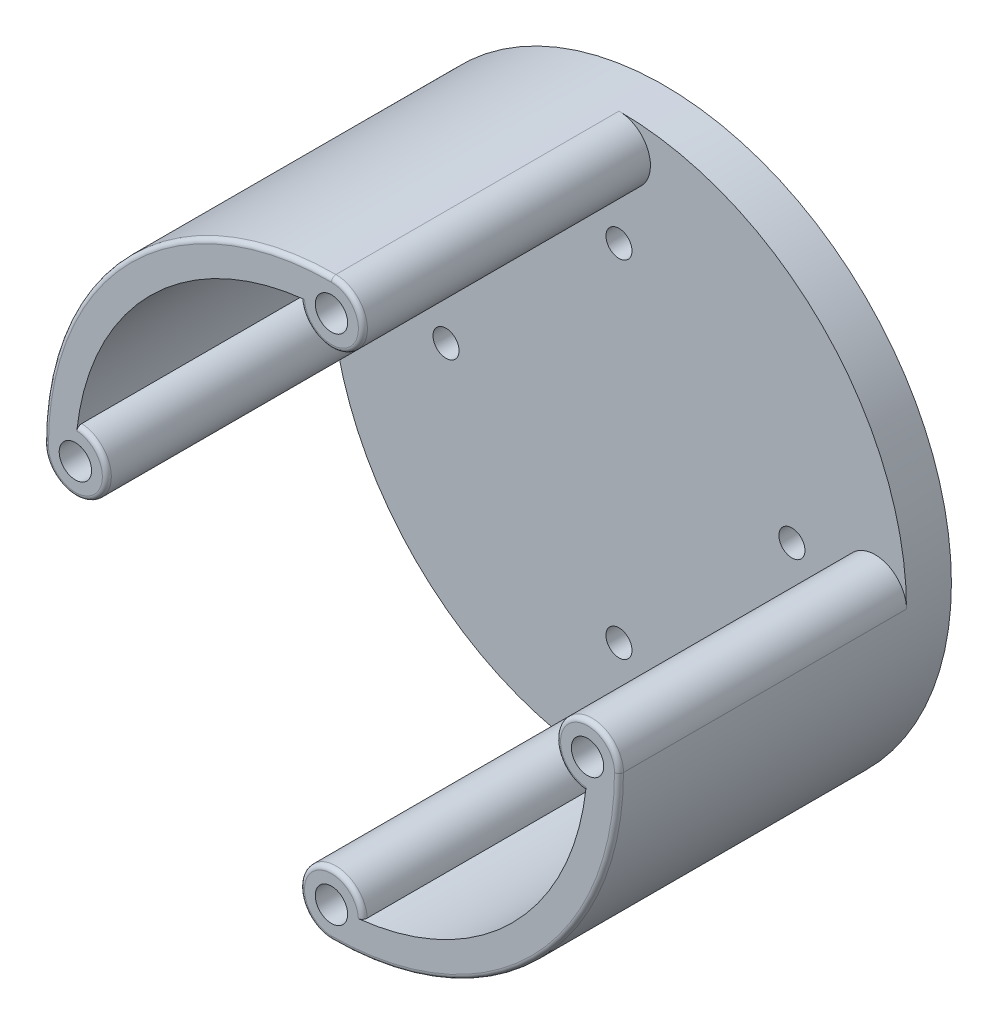
SolidWorks part; units mm, degrees
ref_plane "前视基准面" through (0, 0, 0) normal (0, 0, 1) x (1, 0, 0)
ref_plane "上视基准面" through (0, 0, 0) normal (0, 1, 0) x (1, 0, 0)
ref_plane "右视基准面" through (0, 0, 0) normal (1, 0, 0) x (0, 0, -1)
other "Configuration Table"
sketch "草图1" plane through (0, 0, 0) normal (0, 0, 1) x (1, 0, 0)
  circle A0 centre (0, 0) radius 32
  circle A1 centre (0, 0) radius 19.25 construction
  circle A2 centre (0, 19.25) radius 1.45
  circle A3 centre (19.25, 0) radius 1.45
  circle A4 centre (0, -19.25) radius 1.45
  circle A5 centre (-19.25, 0) radius 1.45
  point P15 (0, 0)
  dimension "D1" = 64
  dimension "D2" = 38.5
  dimension "D3" = 2.9
  dimension "D4" = 4
extrude "凸台-拉伸1" add sketch "草图1" along normal blind 5
sketch "草图2" plane through (0, 0, 5) normal (0, 0, 1) x (1, 0, 0)
  circle A0 centre (0, 0) radius 28.5 construction
  circle A1 centre (0, 28.5) radius 1.8
  circle A2 centre (28.5, 0) radius 1.8
  circle A3 centre (0, -28.5) radius 1.8
  circle A4 centre (-28.5, 0) radius 1.8
  point P14 (0, 0)
  dimension "D1" = 57
  dimension "D2" = 3.6
  dimension "D3" = 4
extrude "切除-拉伸1" cut sketch "草图2" against normal blind 3
sketch "草图3" plane through (0, 0, 5) normal (0, 0, 1) x (1, 0, 0)
  circle A0 centre (-28.5, 0) radius 1.8
  circle A1 centre (-28.5, 0) radius 3.5
  circle A2 centre (0, 0) radius 32 construction
  circle A3 centre (0, 28.5) radius 3.5
  circle A4 centre (28.5, 0) radius 3.5
  circle A5 centre (0, -28.5) radius 3.5
  circle A6 centre (0, 28.5) radius 1.8
  circle A7 centre (28.5, 0) radius 1.8
  circle A8 centre (0, -28.5) radius 1.8
  point P15 (0, 0)
  point P22 (0, 0)
  dimension "D1" = 4
  dimension "D2" = 4
extrude "凸台-拉伸2" add sketch "草图3" along normal blind 32
sketch "草图4" plane through (0, 0, 5) normal (0, 0, 1) x (1, 0, 0)
  line L0 (28.5, 0) -> (32, 0)
  line L1 (0, -28.5) -> (0, -32)
  line L2 (-28.5, 0) -> (-32, 0)
  line L3 (0, 28.5) -> (0, 32)
  circle A0 centre (0, 0) radius 28.5
  circle A1 centre (0, 0) radius 32
  arc M5 (0, 32) -> (-32, 0) centre (0, 0) ccw
  circle M6 centre (-28.5, 0) radius 3.5
  circle M8 centre (0, -28.5) radius 3.5
  arc M9 (0, -32) -> (32, 0) centre (0, 0) ccw
  circle M10 centre (28.5, 0) radius 3.5
  circle M12 centre (0, 28.5) radius 3.5
extrude "凸台-拉伸3" add sketch "草图4" along normal blind 32 contours A0 M8 M9 M10 | A0 M12 M5 M6 region at (22.3074, -22.3074, 5) region at (-2.8794, 31.2077, 5)
sketch "草图5" plane through (0, 0, 0) normal (0, 0, -1) x (-1, 0, 0)
  circle A0 centre (0, 0) radius 28.5 construction
  circle A1 centre (28.5, 0) radius 3
  circle A2 centre (0, -28.5) radius 3
  circle A3 centre (-28.5, 0) radius 3
  circle A4 centre (0, 28.5) radius 3
  point P15 (0, 0)
  dimension "D1" = 6
  dimension "D2" = 4
extrude "切除-拉伸2" cut sketch "草图5" against normal blind 8
hole_wizard "M2.5 十字槽半沉头木螺钉的锥形沉头孔1" positions "草图8" profile "草图9" countersink size "M2.5" standard "GB" end condition through all
sketch "草图8" plane through (0, 0, 0) normal (0, 0, -1) x (-1, 0, 0)
  point P0 (-19.25, 0)
  point P3 (0, -19.25)
  point P6 (19.25, 0)
  point P9 (0, 19.25)
sketch "草图9" plane through (19.25, 0, 0) normal (1, 0, 0) x (0, 1, 0)
  line L0 (0, 0) -> (0, 37)
  line L1 (0, 37) -> (1.45, 37)
  line L2 (1.45, 37) -> (1.45, 1.25)
  line L3 (1.45, 1.25) -> (2.7, 0)
  line L5 (2.7, 0) -> (0, 0)
  line L6 (-1.45, 1.25) -> (-2.7, 0) construction
  line L11 (0, -6.35) -> (0, 107.95) construction
  dimension "通孔孔直径" = 2.9
  dimension "通孔孔深度" = 37
  dimension "近端锥形沉头孔直径" = 5.4
  dimension "近端锥形沉头孔角度" = 90
fillet "圆角1" radius 0.5 6 edges at (2.5497, 26.1023, 37) (-26.1023, -2.5497, 37) (-2.5497, -26.1023, 37) (22.6274, -22.6274, 37) (-22.6274, 22.6274, 37) (26.1023, 2.5497, 37)
